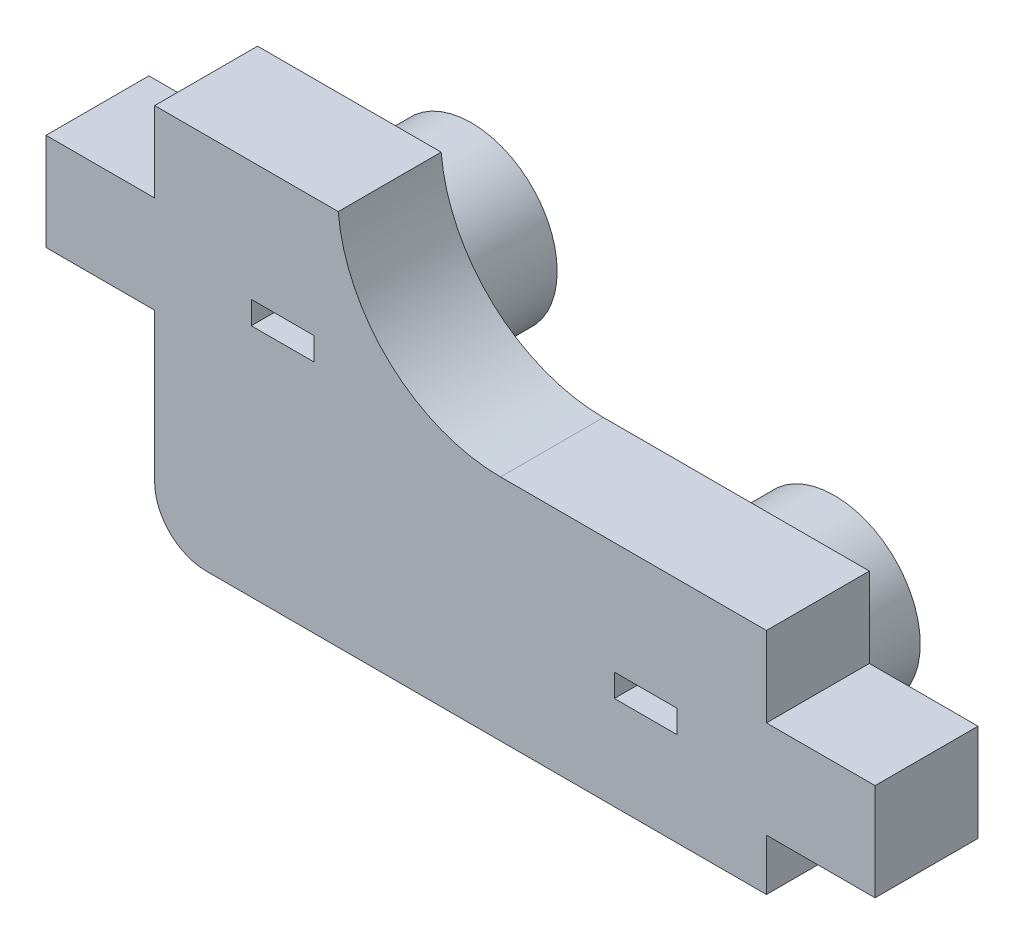
SolidWorks part; units mm, degrees
ref_plane "前视基准面" through (0, 0, 0) normal (0, 0, 1) x (1, 0, 0)
ref_plane "上视基准面" through (0, 0, 0) normal (0, 1, 0) x (1, 0, 0)
ref_plane "右视基准面" through (0, 0, 0) normal (1, 0, 0) x (0, 0, -1)
other "Configuration Table"
sketch "草图1" plane through (0, 0, 0) normal (0, 0, 1) x (1, 0, 0)
  line L0 (-6.05, -0.25) -> (-2.839, -0.25)
  line L1 (0, -2.85) -> (4.65, -2.85)
  line L2 (4.65, -2.85) -> (4.65, -4.25)
  line L3 (4.65, -4.25) -> (6.55, -4.25)
  line L4 (6.55, -4.25) -> (6.55, -5.95)
  line L5 (6.55, -5.95) -> (4.65, -5.95)
  line L6 (4.65, -5.95) -> (4.65, -6.85)
  line L7 (4.65, -6.85) -> (-5.15, -6.85)
  line L9 (-6.05, -0.25) -> (-6.05, -1.65)
  line L10 (-6.05, -1.65) -> (-7.95, -1.65)
  line L11 (-7.95, -1.65) -> (-7.95, -3.35)
  line L12 (-7.95, -3.35) -> (-6.05, -3.35)
  line L13 (-6.05, -3.35) -> (-6.05, -5.95)
  circle A0 centre (0, 0) radius 2.05
  circle A1 centre (0, 0) radius 2.85
  circle A3 centre (-5.15, -5.95) radius 0.9
  point P5 (0, 0)
  dimension "D1" = 4.1
  dimension "D2" = 4
  dimension "D4" = 10.7
  dimension "D5" = 0.8
  dimension "D3" = 7.8692
  dimension "D6" = 1.7
  dimension "D7" = 14.5
  dimension "D8" = 0.9
  dimension "D9" = 3.5
extrude "凸台-拉伸1" add sketch "草图1" along normal blind 1.8 contours A3 L7 L6 L5 L4 L3 L2 L1 A1 L9 L10 L11 L12 L13 | A3 region at (-1.0819, -4.109, 0) region at (-5.15, -5.95, 0)
sketch "草图2" plane through (0, 0, 0) normal (0, 0, -1) x (-1, 0, 0)
  line L1 (-3.09, -5.21) -> (-1.99, -5.21)
  line L2 (-3.09, -5.21) -> (-3.09, -4.81)
  line L3 (-3.09, -4.81) -> (-1.99, -4.81)
  line L4 (-1.99, -5.21) -> (-1.99, -4.81)
  line L5 (-3.09, -5.21) -> (-1.99, -4.81) construction
  line L6 (-3.09, -4.81) -> (-1.99, -5.21) construction
  line L7 (3.26, -2.74) -> (4.36, -2.74)
  line L8 (3.26, -2.74) -> (3.26, -2.34)
  line L9 (3.26, -2.34) -> (4.36, -2.34)
  line L10 (4.36, -2.74) -> (4.36, -2.34)
  line L11 (3.26, -2.74) -> (4.36, -2.34) construction
  line L12 (3.26, -2.34) -> (4.36, -2.74) construction
  circle A0 centre (-2.54, -5.01) radius 1.5
  circle A1 centre (3.81, -2.54) radius 1.5
  dimension "D5" = 3
  dimension "D1" = 5.01
  dimension "D2" = 2.54
  dimension "D3" = 3.81
  dimension "D4" = 2.54
  dimension "D6" = 1.1
  dimension "D7" = 0.4
extrude "凸台-拉伸2" add sketch "草图2" along normal blind 1.5 contours A1 | A0
extrude "切除-拉伸1" cut sketch "草图2<3>" against normal through all contours L7 L10 L9 L8 | L1 L4 L3 L2
sketch "草图2<3>" plane through (0, 0, 0) normal (0, 0, -1) x (-1, 0, 0) same geometry as "草图2"
